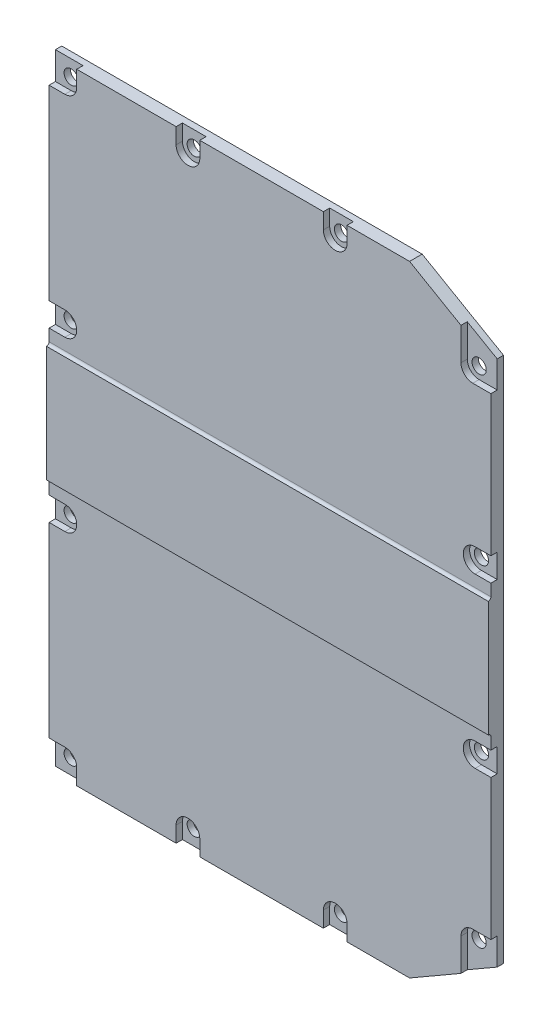
SolidWorks part; units mm, degrees
material "Nylon 101"
ref_plane "Front Plane" through (0, 0, 0) normal (0, 0, 1) x (1, 0, 0)
ref_plane "Top Plane" through (0, 0, 0) normal (0, 1, 0) x (1, 0, 0)
ref_plane "Right Plane" through (0, 0, 0) normal (1, 0, 0) x (0, 0, -1)
sketch "Sketch1" plane through (0, 0, 0) normal (0, 0, 1) x (1, 0, 0)
  line L6 (6.35, 177.673) -> (6.35, -9.652)
  line L7 (115.1507, 177.673) -> (6.35, 177.673)
  line L8 (139.7, 163.4995) -> (115.1507, 177.673)
  line L9 (139.7, 4.5215) -> (139.7, 163.4995)
  line L10 (115.1507, -9.652) -> (139.7, 4.5215)
  line L11 (6.35, -9.652) -> (115.1507, -9.652)
  line L12 (6.35, 177.673) -> (6.35, -9.652)
  line L13 (115.1507, 177.673) -> (6.35, 177.673)
  line L14 (139.7, 163.4995) -> (115.1507, 177.673)
  line L15 (139.7, 4.5215) -> (139.7, 163.4995)
  line L16 (115.1507, -9.652) -> (139.7, 4.5215)
  line L17 (6.35, -9.652) -> (115.1507, -9.652)
  dimension "D1" = 0
extrude "Boss-Extrude1" add sketch "Sketch1" along normal up to surface (3.81 mm away)
sketch "Sketch2" plane through (0, 0, 3.81) normal (0, 0, 1) x (1, 0, 0)
  line L4 (139.7, 66.548) -> (139.7, 101.473)
  line L5 (139.7, 101.473) -> (6.35, 101.473)
  line L6 (6.35, 101.473) -> (6.35, 66.548)
  line L7 (6.35, 66.548) -> (139.7, 66.548)
  line L8 (139.7, 66.548) -> (139.7, 101.473)
  line L9 (139.7, 101.473) -> (6.35, 101.473)
  line L10 (6.35, 101.473) -> (6.35, 66.548)
  line L11 (6.35, 66.548) -> (139.7, 66.548)
  dimension "D1" = 0
extrude "Boss-Extrude2" add sketch "Sketch2" along normal blind 0.7937
hole_wizard "CBORE for #6 Socket Head Cap Screw1" positions "Sketch4" profile "Sketch3" counterbore size "#6" standard "ANSI Inch"
sketch "Sketch4" plane through (0, 0, 3.81) normal (0, 0, 1) x (1, 0, 0)
  point P0 (134.9375, 58.6105)
  point P3 (134.9375, 109.4105)
  point P6 (134.239, 158.9405)
  point P9 (92.71, 172.9105)
  point P12 (48.26, 172.9105)
  point P15 (11.1125, 172.9105)
  point P18 (11.1125, 109.4105)
  point P21 (11.1125, 58.6105)
  point P24 (11.1125, -4.8895)
  point P27 (48.26, -4.8895)
  point P30 (92.71, -4.8895)
  point P33 (134.239, 9.0805)
sketch "Sketch3" plane through (134.9375, 58.6105, 3.81) normal (1, 0, 0) x (0, -1, 0)
  line L0 (0, 0) -> (0, 7.6434)
  line L1 (0, 7.6434) -> (2.1526, 6.35)
  line L2 (2.1526, 6.35) -> (2.1526, 1.905)
  line L3 (2.1526, 1.905) -> (3.5725, 1.905)
  line L4 (3.5725, 1.905) -> (3.5725, 0)
  line L5 (3.5725, 0) -> (0, 0)
  line L10 (0, 7.6434) -> (-2.1527, 6.35) construction
  line L11 (0, -6.35) -> (0, 107.95) construction
  dimension "Hole Dia." = 4.3053
  dimension "Hole Depth" = 6.35
  dimension "C'Bore Dia." = 7.145
  dimension "C'Bore Depth" = 1.905
  dimension "Drill Angle" = 118
fillet "Fillet1" radius 0.7937 2 edges
sketch "Sketch5" plane through (0, 0, 3.81) normal (0, 0, 1) x (1, 0, 0)
  line L0 (134.9375, 58.6105) -> (139.7, 58.6105) construction
  line L1 (134.9375, 62.183) -> (139.7, 62.183)
  line L2 (134.9375, 55.038) -> (139.7, 55.038)
  line L3 (139.7, 4.5215) -> (139.7, 65.7543) construction
  line L4 (73.025, 84.0105) -> (73.025, -9.652) construction
  line L5 (134.9375, 109.4105) -> (139.7, 109.4105) construction
  line L6 (6.35, 84.0105) -> (139.7, 84.0105) construction
  line L7 (6.35, 101.473) -> (6.35, 66.548) construction
  line L8 (139.7, 66.548) -> (139.7, 101.473) construction
  line L9 (6.35, -9.652) -> (115.1507, -9.652) construction
  line L10 (11.1125, 58.6105) -> (6.35, 58.6105) construction
  line L11 (11.1125, 62.183) -> (6.35, 62.183)
  line L12 (11.1125, 55.038) -> (6.35, 55.038)
  line L13 (11.1125, -1.317) -> (6.35, -1.317)
  line L14 (6.35, 65.7543) -> (6.35, -9.652) construction
  line L15 (6.35, -1.317) -> (6.35, -9.652)
  line L16 (6.35, -9.652) -> (14.685, -9.652)
  line L17 (14.685, -4.8895) -> (14.685, -9.652)
  line L18 (48.26, -4.8895) -> (48.26, -9.652) construction
  line L19 (51.8325, -4.8895) -> (51.8325, -9.652)
  line L20 (44.6875, -4.8895) -> (44.6875, -9.652)
  line L21 (92.71, -4.8895) -> (92.71, -9.652) construction
  line L22 (96.2825, -4.8895) -> (96.2825, -9.652)
  line L23 (89.1375, -4.8895) -> (89.1375, -9.652)
  line L24 (130.6665, 9.0805) -> (130.6665, -0.694)
  line L25 (115.1507, -9.652) -> (139.7, 4.5215) construction
  line L26 (130.6665, -0.694) -> (139.7, 4.5215)
  line L27 (139.7, 4.5215) -> (139.7, 12.653)
  line L28 (139.7, 12.653) -> (134.239, 12.653)
  line L29 (134.9375, 105.838) -> (139.7, 105.838)
  line L30 (134.9375, 112.983) -> (139.7, 112.983)
  line L31 (11.1125, 109.4105) -> (6.35, 109.4105) construction
  line L32 (11.1125, 105.838) -> (6.35, 105.838)
  line L33 (11.1125, 112.983) -> (6.35, 112.983)
  line L34 (48.26, 172.9105) -> (48.26, 177.673) construction
  line L35 (51.8325, 172.9105) -> (51.8325, 177.673)
  line L36 (44.6875, 172.9105) -> (44.6875, 177.673)
  line L37 (92.71, 172.9105) -> (92.71, 177.673) construction
  line L38 (96.2825, 172.9105) -> (96.2825, 177.673)
  line L39 (89.1375, 172.9105) -> (89.1375, 177.673)
  line L40 (139.7, 155.368) -> (134.239, 155.368)
  line L41 (139.7, 163.4995) -> (139.7, 155.368)
  line L42 (130.6665, 168.715) -> (139.7, 163.4995)
  line L43 (130.6665, 158.9405) -> (130.6665, 168.715)
  line L44 (14.685, 172.9105) -> (14.685, 177.673)
  line L45 (6.35, 177.673) -> (14.685, 177.673)
  line L46 (6.35, 169.338) -> (6.35, 177.673)
  line L47 (11.1125, 169.338) -> (6.35, 169.338)
  arc A0 (134.9375, 62.183) -> (134.9375, 55.038) centre (134.9375, 58.6105) ccw
  arc A1 (139.7, 55.038) -> (139.7, 62.183) centre (139.7, 58.6105) ccw
  circle A2 centre (134.9375, 58.6105) radius 3.5725 construction
  arc A3 (11.1125, 62.183) -> (11.1125, 55.038) centre (11.1125, 58.6105) cw
  arc A4 (6.35, 55.038) -> (6.35, 62.183) centre (6.35, 58.6105) cw
  arc A5 (14.685, -4.8895) -> (11.1125, -1.317) centre (11.1125, -4.8895) ccw
  circle A6 centre (11.1125, -4.8895) radius 3.5725 construction
  arc A7 (51.8325, -4.8895) -> (44.6875, -4.8895) centre (48.26, -4.8895) ccw
  arc A8 (44.6875, -9.652) -> (51.8325, -9.652) centre (48.26, -9.652) ccw
  arc A9 (96.2825, -4.8895) -> (89.1375, -4.8895) centre (92.71, -4.8895) ccw
  arc A10 (89.1375, -9.652) -> (96.2825, -9.652) centre (92.71, -9.652) ccw
  arc A11 (134.239, 12.653) -> (130.6665, 9.0805) centre (134.239, 9.0805) ccw
  circle A12 centre (134.239, 9.0805) radius 3.5725 construction
  arc A13 (134.9375, 105.838) -> (134.9375, 112.983) centre (134.9375, 109.4105) cw
  arc A14 (139.7, 112.983) -> (139.7, 105.838) centre (139.7, 109.4105) cw
  arc A15 (11.1125, 105.838) -> (11.1125, 112.983) centre (11.1125, 109.4105) ccw
  arc A16 (6.35, 112.983) -> (6.35, 105.838) centre (6.35, 109.4105) ccw
  arc A17 (51.8325, 172.9105) -> (44.6875, 172.9105) centre (48.26, 172.9105) cw
  arc A18 (44.6875, 177.673) -> (51.8325, 177.673) centre (48.26, 177.673) cw
  arc A19 (96.2825, 172.9105) -> (89.1375, 172.9105) centre (92.71, 172.9105) cw
  arc A20 (89.1375, 177.673) -> (96.2825, 177.673) centre (92.71, 177.673) cw
  arc A21 (134.239, 155.368) -> (130.6665, 158.9405) centre (134.239, 158.9405) cw
  arc A22 (14.685, 172.9105) -> (11.1125, 169.338) centre (11.1125, 172.9105) cw
  point P3 (137.3188, 58.6105)
  point P25 (8.7313, 58.6105)
  point P45 (48.26, -7.2708)
  point P50 (92.71, -7.2708)
  point P71 (137.3188, 109.4105)
  point P78 (8.7313, 109.4105)
  point P85 (48.26, 175.2918)
  point P92 (92.71, 175.2918)
extrude "Cut-Extrude1" cut sketch "Sketch5" against normal up to surface (1.905 mm away) up to face at (137.0902, 58.6105, 1.905)
